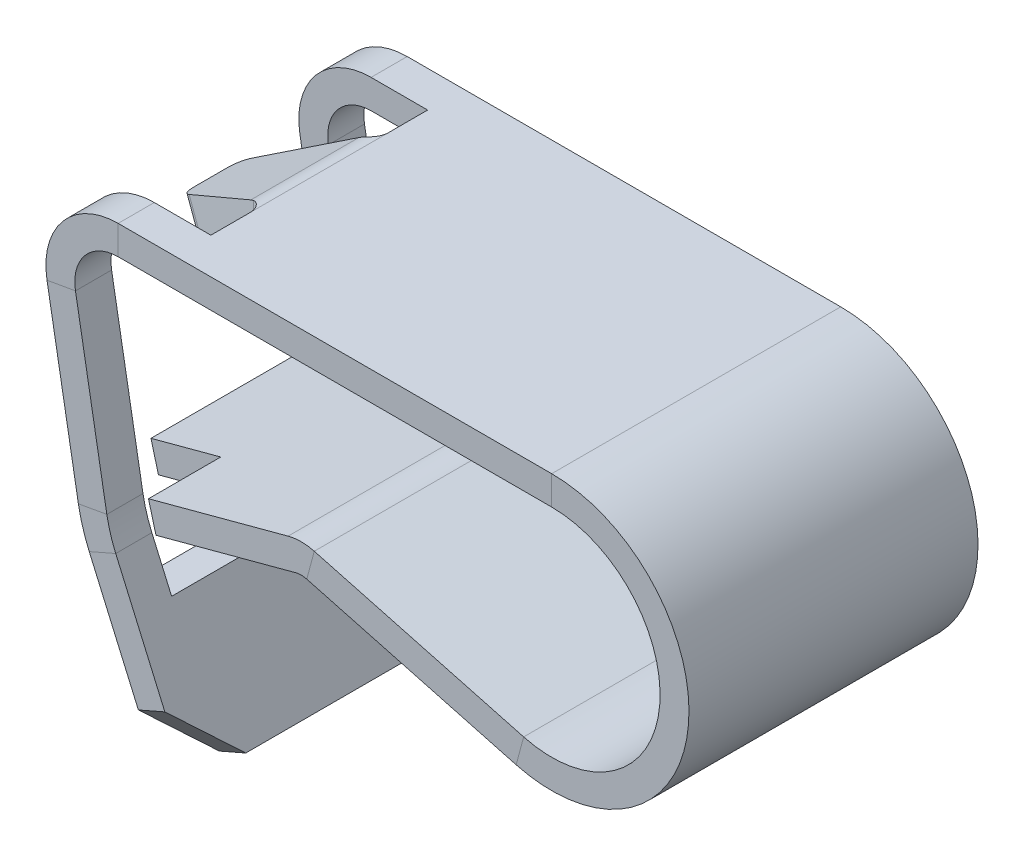
SolidWorks part; units mm, degrees
material "Chrome Stainless Steel"
ref_plane "Front Plane" through (0, 0, 0) normal (0, 0, 1) x (1, 0, 0)
ref_plane "Top Plane" through (0, 0, 0) normal (0, 1, 0) x (1, 0, 0)
ref_plane "Right Plane" through (0, 0, 0) normal (1, 0, 0) x (0, 0, -1)
sketch "MainProfilePath" plane through (0, 0, 0) normal (0, 0, 1) x (1, 0, 0)
  line L0 (0, 0) -> (-1, 2.2913)
  line L1 (-1.1366, 2.744) -> (-1.5707, 5.206)
  line L2 (0, 0) -> (0, 2.2913) construction
  line L3 (-1, 2.2913) -> (0, 2.2913) construction
  line L4 (-0.7829, 6.1449) -> (5.2171, 6.1449)
  line L5 (4.7771, 2.8029) -> (1.8794, 3.5793)
  line L6 (1.6206, 3.5793) -> (-1.2772, 2.8029)
  line L7 (1.75, 3.5963) -> (1.75, 6.1449) construction
  arc A0 (-1.5707, 5.206) -> (-0.7829, 6.1449) centre (-0.7829, 5.3449) cw
  arc A1 (5.2171, 6.1449) -> (4.7771, 2.8029) centre (5.2171, 4.4449) cw
  arc A2 (-1.1366, 2.744) -> (-1, 2.2913) centre (0.833, 3.0913) ccw
  arc A3 (1.6206, 3.5793) -> (1.8794, 3.5793) centre (1.75, 3.0963) cw
  point P19 (1.75, 3.5963)
  dimension "D1" = 2.5
  dimension "D2" = 2
  dimension "D3" = 1
  dimension "D4" = 2.5
  dimension "D6" = 0.8
  dimension "D8" = 1.7
  dimension "D9" = 0.5
  dimension "D5" = 10
  dimension "D7" = 6
  dimension "D10" = 15
  dimension "D11" = 3
  dimension "D12" = 3
  dimension "D13" = 15
ref_plane "ProfileP" through (0, 0, 0) normal (-0.4, 0.9165, 0) x (0.9165, 0.4, 0)
sketch "MainProfileS" plane through (0, 0, 0) normal (-0.4, 0.9165, 0) x (0.9165, 0.4, 0)
  line L1 (-0.2, -2) -> (0.2, -2)
  line L2 (-0.2, -2) -> (-0.2, 2)
  line L3 (-0.2, 2) -> (0.2, 2)
  line L4 (0.2, -2) -> (0.2, 2)
  line L5 (-0.2, -2) -> (0.2, 2) construction
  line L6 (-0.2, 2) -> (0.2, -2) construction
  point P0 (0, 0)
  dimension "Width" = 0.4
  dimension "Length" = 4
sweep "MainProfile" add profiles "MainProfileS" path "MainProfilePath"
sketch "ConnectionAccessS" plane through (0, 0, 0) normal (1, 0, 0) x (0, 0, -1)
  line L0 (2, 6.3449) -> (-2, 6.3449) construction
  line L1 (1.5, 6.3449) -> (-1.5, 6.3449)
  line L2 (1.5, 6.3449) -> (1.5, 1.7449)
  line L3 (1.5, 1.7449) -> (-1.5, 1.7449)
  line L4 (-1.5, 6.3449) -> (-1.5, 1.7449)
  line L5 (0, 0) -> (0, 1.7449) construction
  line L7 (2, 2.7093) -> (2, 5.1713) construction
  dimension "D1" = 0.5
  dimension "D2" = 3
  dimension "D3" = 4.6
extrude "ConnectionAccess" cut sketch "ConnectionAccessS" against normal up to next
sketch "EndProfilePath" plane through (0, 0, 0) normal (0, 0, 1) x (1, 0, 0)
  line L1 (1.6206, 3.5793) -> (-0.3113, 3.0617)
  line L2 (1.6206, 3.5793) -> (-1.2772, 2.8029) construction
  dimension "D1" = 2
sketch "EndProfileS" plane through (2.4068, 0.6449, 0) normal (-0.9659, -0.2588, 0) x (0, 0, 1)
  line L0 (-2, 2.8379) -> (2, 2.8379) construction
  line L1 (-2, 3.2379) -> (2, 3.2379)
  line L2 (-2, 3.2379) -> (-2, 2.8379)
  line L3 (-2, 2.8379) -> (2, 2.8379)
  line L4 (2, 3.2379) -> (2, 2.8379)
  line L5 (-2, 3.2379) -> (2, 2.8379) construction
  line L6 (-2, 2.8379) -> (2, 3.2379) construction
  point P0 (0, 3.0379)
sweep "EndProfile" add profiles "EndProfileS" path "EndProfilePath"
sketch "EndConnectionS" plane through (0.475, 0.1273, 0) normal (-0.9659, -0.2588, 0) x (0, 0, 1)
  line L0 (-2, 2.8379) -> (2, 2.8379) construction
  line L1 (-1, 3.2379) -> (1, 3.2379)
  line L2 (-1, 3.2379) -> (-1, 2.8379)
  line L3 (-1, 2.8379) -> (1, 2.8379)
  line L4 (1, 3.2379) -> (1, 2.8379)
  line L5 (-1, 3.2379) -> (1, 2.8379) construction
  line L6 (-1, 2.8379) -> (1, 3.2379) construction
  point P0 (0, 3.0379)
  dimension "D1" = 2
sketch "EndConnectionPath" plane through (0, 0, 0) normal (0, 0, 1) x (1, 0, 0)
  line L1 (-0.3113, 3.0617) -> (-1.2772, 2.8029)
  line L2 (-0.2595, 2.8685) -> (-0.3631, 3.2549) construction
  line L3 (1.6206, 3.5793) -> (-1.2772, 2.8029) construction
sweep "EndConnection" add profiles "EndConnectionS" path "EndConnectionPath"
sketch "LockingTabS" plane through (0, 0, 0) normal (-1, 0, 0) x (0, 0, 1)
  line L0 (-1.5, 5.9449) -> (1.5, 5.9449) construction
  line L1 (-0.8, 6.3449) -> (0.8, 6.3449)
  line L2 (-0.8, 6.3449) -> (-0.8, 5.9449)
  line L3 (-0.8, 5.9449) -> (0.8, 5.9449)
  line L4 (0.8, 6.3449) -> (0.8, 5.9449)
  line L5 (-0.8, 6.3449) -> (0.8, 5.9449) construction
  line L6 (-0.8, 5.9449) -> (0.8, 6.3449) construction
  line L7 (-1.5, 6.3449) -> (1.5, 6.3449) construction
  point P0 (0, 6.1449)
  dimension "Length" = 1.6
sketch "LockingTabPath" plane through (0, 0, 0) normal (0, 0, 1) x (1, 0, 0)
  line L0 (-0.1, 6.1181) -> (-1.3988, 5.3682)
  line L1 (-0.7829, 6.1449) -> (5.2171, 6.1449) construction
  line L5 (-0.7829, 6.3449) -> (0, 6.3449) construction
  arc A0 (-0.1, 6.1181) -> (0, 6.1449) centre (0, 5.9449) cw
  dimension "D1" = 0.2
  dimension "D2" = 30
  dimension "D3" = 1.6
sweep "LockingTab" add profiles "LockingTabS" path "LockingTabPath"
sketch "LTCutS" plane through (2.9725, 6.3449, 0) normal (0, -1, 0) x (-1, 0, 0)
  line L0 (2.9725, 0.8) -> (4.4713, 0.4)
  line L1 (4.4713, -0.8) -> (4.4713, 0.8) construction
  line L2 (4.4713, 0.4) -> (4.4713, 0.8)
  line L3 (4.4713, 0.8) -> (2.9725, 0.8)
  dimension "D1" = 0.4
extrude "LTCut" cut sketch "LTCutS" along normal up to next
mirror "LTCutHM" about plane through (0, 0, 0) normal (0, 0, 1) of "LTCut"
fillet "LTCutF" radius 0.2 4 edges at (-1.3988, 5.3682, 0.4267) (-1.3988, 5.3682, -0.4267) (0, 6.1449, 0.8) (0, 6.1449, -0.8)
chamfer "MPC" distance 0.8 angle 45 2 edges at (0, 0, -2) (0, 0, 2)
